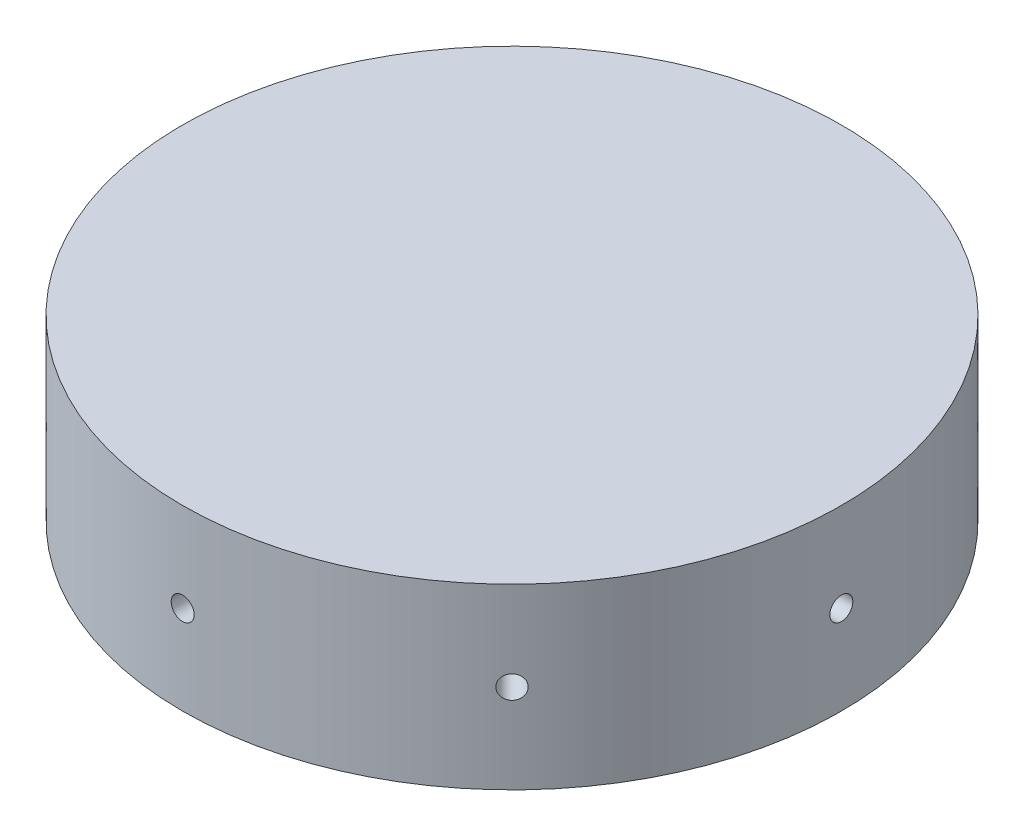
SolidWorks part; units mm, degrees
material "6061 Alloy"
ref_plane "Front Plane" through (0, 0, 0) normal (0, 0, 1) x (1, 0, 0)
ref_plane "Top Plane" through (0, 0, 0) normal (0, 1, 0) x (1, 0, 0)
ref_plane "Right Plane" through (0, 0, 0) normal (1, 0, 0) x (0, 0, -1)
sketch "Sketch1" plane through (0, 0, 0) normal (0, 1, 0) x (1, 0, 0)
  circle A0 centre (0, 0) radius 46.99
  dimension "D1" = 93.98
extrude "Bulkhead Extrusion" add sketch "Sketch1" along normal blind 25.4
ref_plane "Plane1" through (0, 0, 46.99) normal (0, 0, 1) x (1, 0, 0)
sketch "Sketch2" plane through (0, 0, 46.99) normal (0, 0, 1) x (1, 0, 0)
  line L0 (0, 25.4) -> (0, 0) construction
  line L1 (46.99, 25.4) -> (-46.99, 25.4) construction
  circle A0 centre (0, 12.7) radius 1.6383
  dimension "D1" = 3.2766
extrude "Screw Hole" cut sketch "Sketch2" against normal blind 12.7
pattern_circular "CirPattern1" count 8 over 360 about axis through (0, 25.4, 0) along (0, -1, 0) of "Screw Hole" reverse direction yes
